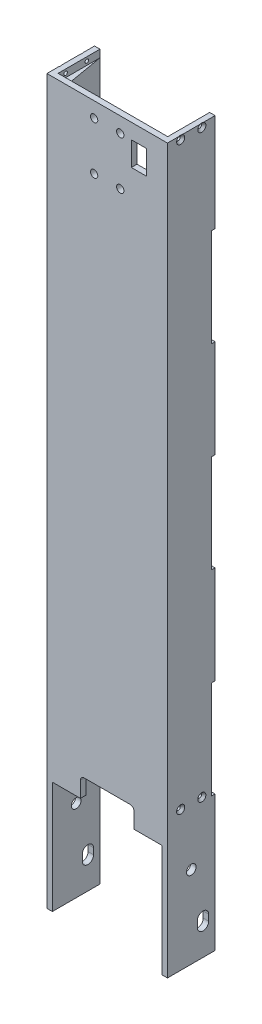
SolidWorks part; units mm, degrees
ref_plane "Front Plane" through (0, 0, 0) normal (0, 0, 1) x (1, 0, 0)
ref_plane "Top Plane" through (0, 0, 0) normal (0, 1, 0) x (1, 0, 0)
ref_plane "Right Plane" through (0, 0, 0) normal (1, 0, 0) x (0, 0, -1)
sketch "Sketch1" plane through (0, 0, 0) normal (0, 1, 0) x (1, 0, 0)
  line L0 (0, 0) -> (0, 40.132)
  line L1 (0, 0) -> (101.6, 0)
  line L2 (101.6, 0) -> (101.6, 40.132)
  line L3 (85.5838, 4.8006) -> (16.0162, 4.8006)
  line L6 (2.032, 40.132) -> (0, 40.132)
  line L7 (99.568, 40.132) -> (101.6, 40.132)
  line L10 (99.568, 40.132) -> (97.028, 40.132)
  line L12 (2.032, 40.132) -> (4.572, 40.132)
  line L14 (9.7587, 10.0709) -> (4.572, 40.132)
  line L16 (97.028, 40.132) -> (91.8413, 10.0709)
  arc A0 (91.8413, 10.0709) -> (85.5838, 4.8006) centre (85.5838, 11.1506) cw
  arc A1 (16.0162, 4.8006) -> (9.7587, 10.0709) centre (16.0162, 11.1506) cw
  dimension "D1" = 40.132
extrude "Boss-Extrude1" add sketch "Sketch1" along normal blind 609.6
sketch "Sketch5" plane through (0, 0, 0) normal (0, -1, 0) x (1, 0, 0)
  line L0 (4.572, -40.132) -> (4.572, 0)
  line L1 (0, 0) -> (101.6, 0) construction
  line L2 (4.572, 0) -> (97.028, 0)
  line L3 (97.028, 0) -> (97.028, -40.132)
  line L4 (97.028, -40.132) -> (4.572, -40.132)
extrude "Cut-Extrude4" cut sketch "Sketch5" against normal blind 94.488
sketch "Sketch6" plane through (0, 0, 0) normal (0, 0, 1) x (1, 0, 0)
  line L0 (50.8, 94.488) -> (50.8, 108.0418) construction
  line L1 (73.3582, 94.488) -> (28.2418, 94.488)
  line L2 (28.2418, 110.9736) -> (73.3582, 110.9736)
  line L3 (101.6, 609.6) -> (101.6, 564.6379) construction
  line L4 (61.8109, 596.7967) -> (61.8109, 516.66) construction
  line L5 (50.8, 609.6) -> (50.8, 495.0113) construction
  line L6 (71.1581, 596.7967) -> (71.1581, 576.5402)
  line L7 (71.1581, 576.5402) -> (83.8581, 576.5402)
  line L8 (83.8581, 576.5402) -> (83.8581, 596.7967)
  line L9 (83.8581, 596.7967) -> (71.1581, 596.7967)
  line L10 (50.8, 94.488) -> (50.8, 108.0418) construction
  line L11 (97.028, 94.488) -> (4.572, 94.488) construction
  line L12 (71.1581, 576.5402) -> (30.4419, 576.5402) construction
  line L13 (73.3582, 94.488) -> (73.3582, 110.9736)
  line L14 (71.1581, 576.5402) -> (71.1581, 609.6) construction
  line L16 (0, 609.6) -> (101.6, 609.6) construction
  line L17 (28.2418, 110.9736) -> (28.2418, 94.488)
  line L18 (50.8, 110.9337) -> (50.8, 120.027) construction
  circle A2 centre (39.7891, 596.7967) radius 3.0734
  circle A3 centre (39.7891, 556.2837) radius 3.0734
  circle A4 centre (61.8109, 556.2837) radius 3.0734
  circle A5 centre (61.8109, 596.7967) radius 3.0734
  dimension "D4" = 20.2565
  dimension "D2" = 22.0218
  dimension "D3" = 40.513
  dimension "D7" = 40.7162
  dimension "D8" = 20.3581
  dimension "D9" = 12.7
extrude "Cut-Extrude5" cut sketch "Sketch6" against normal through all
sketch "Sketch4" plane through (0, 0, 0) normal (-1, 0, 0) x (0, 0, 1)
  line L0 (-20.066, 0) -> (-20.066, 8.0214) construction
  line L1 (0, 0) -> (-40.132, 0) construction
  line L2 (-20.066, 0) -> (-20.066, 94.488) construction
  line L3 (-40.132, 114.3) -> (0, 114.3) construction
  line L4 (-40.132, 609.6) -> (-40.132, 0) construction
  line L5 (-29.9711, 29.1841) -> (-29.9711, 24.1041) construction
  line L6 (-25.2086, 29.1841) -> (-25.2086, 24.1041)
  line L7 (-34.7336, 29.1841) -> (-34.7336, 24.1041)
  line L8 (-40.132, 26.6441) -> (0, 26.6441) construction
  line L9 (-40.132, 609.6) -> (-40.132, 0) construction
  line L10 (0, 609.6) -> (0, 0) construction
  line L11 (0, 609.6) -> (0, 0) construction
  line L12 (-36.957, 114.3) -> (-36.957, 196.85)
  line L13 (-40.132, 196.85) -> (0, 196.85) construction
  line L14 (-37.592, 196.85) -> (2.54, 196.85) construction
  line L15 (-40.132, 279.4) -> (0, 279.4) construction
  line L16 (-37.592, 279.4) -> (2.54, 279.4) construction
  line L17 (-40.132, 361.95) -> (0, 361.95) construction
  line L18 (-37.592, 361.95) -> (2.54, 361.95) construction
  line L19 (-40.132, 444.5) -> (0, 444.5) construction
  line L20 (-37.592, 444.5) -> (2.54, 444.5) construction
  line L21 (-40.132, 527.05) -> (0, 527.05) construction
  line L22 (-37.592, 527.05) -> (2.54, 527.05) construction
  line L23 (-10.0709, 609.6) -> (-40.132, 609.6) construction
  line L24 (-40.132, 120.65) -> (0, 120.65) construction
  line L25 (-36.957, 114.3) -> (-40.132, 114.3)
  line L26 (-40.132, 114.3) -> (-40.132, 196.85)
  line L27 (-40.132, 279.4) -> (-36.957, 279.4)
  line L28 (-40.132, 527.05) -> (-36.957, 527.05)
  line L29 (-40.132, 444.5) -> (-36.957, 444.5)
  line L30 (-40.132, 361.95) -> (-36.957, 361.95)
  line L31 (-36.957, 279.4) -> (-36.957, 361.95)
  line L32 (-40.132, 279.4) -> (-40.132, 361.95)
  line L33 (-36.957, 444.5) -> (-36.957, 527.05)
  line L34 (-40.132, 444.5) -> (-40.132, 527.05)
  line L35 (-40.132, 196.85) -> (-36.957, 196.85)
  line L36 (-20.8788, 154.3621) -> (-20.8788, 147.5634) construction
  line L37 (-40.132, 603.25) -> (0, 603.25) construction
  line L38 (-40.132, 361.95) -> (0, 361.95) construction
  line L39 (-4.8006, 609.6) -> (-4.8006, 0) construction
  line L40 (0, 609.6) -> (-40.132, 609.6) construction
  line L41 (-28.9814, 117.475) -> (-28.9814, 656.476) construction
  line L42 (-11.1506, 606.425) -> (-11.1506, 117.475) construction
  line L43 (-34.7336, 0) -> (-25.2086, 0)
  line L44 (-34.7336, 0) -> (-25.2086, 0)
  line L46 (-29.9711, 29.1841) -> (-29.9711, 24.1041) construction
  line L48 (-25.2086, 29.1841) -> (-25.2086, 24.1041)
  line L49 (-34.7336, 29.1841) -> (-34.7336, 24.1041)
  circle A0 centre (-20.066, 69.088) radius 4.064
  circle A1 centre (-11.1506, 117.475) radius 1.524
  arc A2 (-25.2086, 29.1841) -> (-34.7336, 29.1841) centre (-29.9711, 29.1841) ccw
  arc A3 (-25.2086, 29.1841) -> (-34.7336, 29.1841) centre (-29.9711, 29.1841) ccw
  circle A4 centre (-28.9814, 117.475) radius 1.524
  circle A5 centre (-11.1506, 606.425) radius 1.524
  circle A6 centre (-28.9814, 606.425) radius 1.524
  arc A7 (-34.7336, 24.1041) -> (-25.2086, 24.1041) centre (-29.9711, 24.1041) ccw
  point P13 (-29.9711, 26.6441)
  point P28 (-25.1015, 609.6)
  point P65 (-25.1015, 609.6)
  point P83 (-29.9711, 26.6441)
  dimension "D3" = 8.128
  dimension "D11" = 3.048
  dimension "D1" = 94.488
  dimension "D2" = 25.4
  dimension "D4" = 114.3
  dimension "D5" = 82.55
  dimension "D8" = 82.55
  dimension "D9" = 3.175
  dimension "D10" = 6.35
  dimension "D12" = 16.0782
  dimension "D13" = 6.35
  dimension "D14" = 6.35
  dimension "D15" = 241.3
  dimension "D16" = 4.8006
  dimension "D6" = 2
  dimension "D7" = 5
extrude "Cut-Extrude3" cut sketch "Sketch4" against normal through all contours L7 L6 A2 | A0 | L26 L35 L12 L25 | L32 L30 L31 L27 | L34 L28 L33 L29 | A4 | A1 | A5 | A6 region at (0, 26.6441, -29.9711) region at (0, 69.088, -20.066)
sketch "Sketch7" plane through (0, 609.6, 0) normal (0, 1, 0) x (1, 0, 0)
  line L0 (4.572, 40.132) -> (4.572, 4.8006)
  line L1 (4.572, 4.8006) -> (97.028, 4.8006)
  line L2 (97.028, 4.8006) -> (97.028, 40.132)
  line L3 (4.572, 40.132) -> (97.028, 40.132)
extrude "Cut-Extrude6" cut sketch "Sketch7" against normal blind 6.35
sketch "Sketch8" plane through (0, 94.488, 0) normal (0, -1, 0) x (1, 0, 0)
  line L0 (4.572, -40.132) -> (4.572, -4.8006)
  line L1 (4.572, -4.8006) -> (97.028, -4.8006)
  line L2 (97.028, -4.8006) -> (97.028, -40.132)
  line L3 (97.028, -40.132) -> (4.572, -40.132)
extrude "Cut-Extrude7" cut sketch "Sketch8" against normal blind 26.162
sketch "Sketch10" plane through (0, 0, -36.957) normal (0, 0, -1) x (-1, 0, 0)
  line L0 (0, 114.3) -> (0, 196.85) construction
  line L1 (-4.572, 114.3) -> (0, 114.3) construction
  line L2 (0, 114.3) -> (0, 119.0204) construction
  line L3 (0, 279.4) -> (0, 284.1204) construction
  line L4 (0, 444.6204) -> (0, 449.3409) construction
  line L5 (-51.1298, 110.9378) -> (-50.5811, 155.321) construction
  line L7 (-97.028, 114.3) -> (-97.028, 119.0204) construction
  circle A0 centre (-2.286, 155.321) radius 1.1303
  circle A1 centre (-2.286, 320.421) radius 1.1303
  circle A2 centre (-2.286, 485.6414) radius 1.1303
  circle A3 centre (-99.314, 155.321) radius 1.1303
  circle A4 centre (-99.314, 320.421) radius 1.1303
  circle A5 centre (-99.314, 485.6414) radius 1.1303
  dimension "D1" = 2.2606
  dimension "D2" = 2.286
  dimension "D3" = 41.021
extrude "Cut-Extrude8" cut sketch "Sketch10" against normal blind 12.7
chamfer "Chamfer1" distance 1.905 angle 45 8 edges at (101.6, 117.475, -30.5054) (101.6, 117.475, -9.6266) (0, 117.475, -30.5054) (0, 117.475, -9.6266) (0, 606.425, -12.6746) (0, 606.425, -27.4574) (101.6, 606.425, -12.6746) (101.6, 606.425, -27.4574)
fillet "Fillet1" radius 3.175 2 edges at (73.3582, 110.9736, -2.4003) (28.2418, 110.9736, -2.4003)
